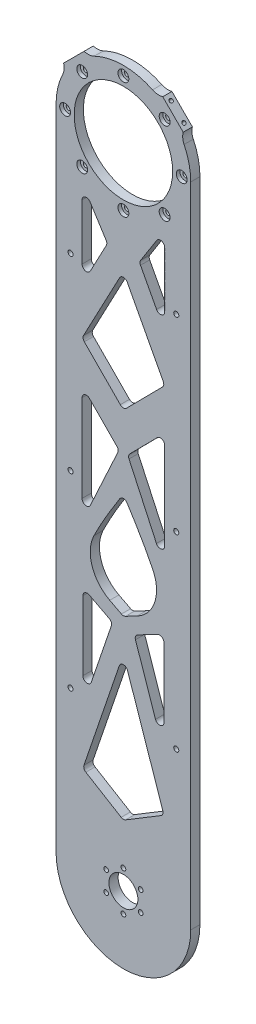
SolidWorks part; units mm, degrees
material "6061-T6 (SS)"
ref_plane "Front Plane" through (0, 0, 0) normal (0, 0, 1) x (1, 0, 0)
ref_plane "Top Plane" through (0, 0, 0) normal (0, 1, 0) x (1, 0, 0)
ref_plane "Right Plane" through (0, 0, 0) normal (1, 0, 0) x (0, 0, -1)
sketch "Sketch2" plane through (0, 0, 0) normal (0, 0, 1) x (1, 0, 0)
  line L0 (0, 0) -> (0, 500) construction
  line L1 (-46.5, 0) -> (-46.5, 500)
  line L2 (46.5, 0) -> (46.5, 500)
  arc A0 (-46.5, 0) -> (46.5, 0) centre (0, 0) ccw
  arc A1 (46.5, 500) -> (-46.5, 500) centre (0, 500) ccw
  circle A2 centre (0, 500) radius 37.25 construction
  circle A3 centre (0, 0) radius 10
  circle A4 centre (0, 13.75) radius 1.65
  circle A5 centre (0, 0) radius 13.75 construction
  circle A6 centre (11.9078, 6.875) radius 1.65
  circle A7 centre (11.9078, -6.875) radius 1.65
  circle A8 centre (0, -13.75) radius 1.65
  circle A9 centre (-11.9078, -6.875) radius 1.65
  circle A10 centre (-11.9078, 6.875) radius 1.65
  point P3 (0, 250)
  point P27 (0, 0)
  dimension "D2" = 74.5
  dimension "D4" = 20
  dimension "D5" = 3.3
  dimension "D6" = 27.5
  dimension "D3" = 46.5
  dimension "D1" = 500
  dimension "D7" = 6
extrude "Boss-Extrude1" add sketch "Sketch2" along normal blind 6.35
sketch "Sketch4" plane through (0, 0, 6.35) normal (0, 0, 1) x (1, 0, 0)
  line L0 (0, 500) -> (0, 999.1647) construction
  line L29 (46.5, 500) -> (-46.5, 500) construction
  line L31 (28.0053, 59.376) -> (0, 42.4117)
  line L32 (0, 141.6934) -> (28.0053, 59.376)
  line L33 (-28.0053, 59.376) -> (0, 141.6934)
  line L34 (0, 42.4117) -> (-28.0053, 59.376)
  line L35 (-7.5, 156.9059) -> (-28.0053, 96.6336)
  line L36 (-28.0053, 167.5829) -> (-7.5, 156.9059)
  line L37 (-28.0053, 96.6336) -> (-28.0053, 167.5829)
  line L38 (28.0053, 167.5829) -> (7.5, 156.9059)
  line L39 (28.0053, 96.6336) -> (28.0053, 167.5829)
  line L40 (7.5, 156.9059) -> (28.0053, 96.6336)
  line L41 (0, 164.2751) -> (28.5505, 179.1412)
  line L42 (0, 164.2751) -> (-28.5505, 179.1412)
  line L43 (28.5505, 259.5868) -> (3, 314.9383)
  line L44 (28.5505, 340.7931) -> (28.5505, 259.5868)
  line L45 (3, 314.9383) -> (28.5505, 340.7931)
  line L46 (-3, 314.9383) -> (-28.5505, 340.7931)
  line L47 (-28.5505, 259.5868) -> (-3, 314.9383)
  line L48 (-28.5505, 340.7931) -> (-28.5505, 259.5868)
  line L49 (0, 423.1428) -> (-28.5505, 369.2462)
  line L50 (-28.5505, 369.2462) -> (0, 340.3557)
  line L51 (0, 340.3557) -> (28.5505, 369.2462)
  line L52 (0, 423.1428) -> (28.5505, 369.2462)
  line L53 (-28.5505, 462.0952) -> (-28.5505, 401.2902)
  line L54 (-11, 434.4215) -> (-28.5505, 462.0952)
  line L55 (-28.5505, 401.2902) -> (-11, 434.4215)
  line L56 (28.5505, 401.2902) -> (11, 434.4215)
  line L57 (28.5505, 462.0952) -> (28.5505, 401.2902)
  line L58 (11, 434.4215) -> (28.5505, 462.0952)
  arc A0 (46.5, 500) -> (-46.5, 500) centre (0, 500) ccw construction
  arc A1 (46.5, 500) -> (-46.5, 500) centre (0, 500) ccw construction
  spline S2 degree 3 poles (28.5505, 179.1412) (45.3203, 216.9857) (19.4301, 259.7903) (0, 290.0258) knots 0 0 0 0 1 1 1 1
  spline S3 degree 3 poles (-28.5505, 179.1412) (-45.3203, 216.9857) (-19.4301, 259.7903) (0, 290.0258) knots 0 0 0 0 1 1 1 1
extrude "Cut-Extrude1" cut sketch "Sketch4" against normal blind 10
fillet "Fillet3" radius 3 30 edges at (-11, 434.4215, 3.175) (-28.5505, 401.2902, 3.175) (28.5505, 401.2902, 3.175) (11, 434.4215, 3.175) (28.5505, 462.0952, 3.175) (-28.5505, 462.0952, 3.175) (0, 423.1428, 3.175) (-28.5505, 369.2462, 3.175) (28.5505, 369.2462, 3.175) (0, 340.3557, 3.175) (28.5505, 340.7931, 3.175) (-28.5505, 340.7931, 3.175) (-3, 314.9383, 3.175) (3, 314.9383, 3.175) (28.5505, 259.5868, 3.175) (-28.5505, 259.5868, 3.175) (28.5505, 179.1412, 3.175) (0, 290.0258, 3.175) (-28.5505, 179.1412, 3.175) (0, 164.2751, 3.175) (-28.0053, 96.6336, 3.175) (28.0053, 96.6336, 3.175) (7.5, 156.9059, 3.175) (-28.0053, 167.5829, 3.175) (28.0053, 167.5829, 3.175) (0, 141.6934, 3.175) (28.0053, 59.376, 3.175) (-28.0053, 59.376, 3.175) (0, 42.4117, 3.175) (-7.5, 156.9059, 3.175)
sketch "Sketch5" plane through (0, 0, 6.35) normal (0, 0, 1) x (1, 0, 0)
  line L0 (0, -46.5) -> (108.8395, -46.5) construction
  line L1 (46.5, 100) -> (-46.5, 100) construction
  line L2 (46.5, 0) -> (46.5, 500) construction
  line L3 (-46.5, 500) -> (-46.5, 0) construction
  line L4 (-46.5, 106.35) -> (46.5, 106.35) construction
  line L5 (36.5, 106.35) -> (36.5, 100) construction
  line L6 (0, 106.35) -> (0, 100) construction
  line L7 (-46.5, 256.35) -> (46.5, 256.35) construction
  line L8 (-46.5, 181.35) -> (46.5, 181.35) construction
  line L9 (-46.5, 337.7) -> (46.5, 337.7) construction
  arc A1 (-46.5, 0) -> (46.5, 0) centre (0, 0) ccw construction
  circle A2 centre (36.5, 103.175) radius 1.75
  circle A3 centre (-36.5, 103.175) radius 1.75
  circle A4 centre (36.5, 259.525) radius 1.75
  circle A5 centre (-36.5, 259.525) radius 1.75
  circle A6 centre (36.5, 415.875) radius 1.75
  circle A7 centre (-36.5, 415.875) radius 1.75
  point P18 (36.5, 103.175)
  dimension "D2" = 3.5
  dimension "D1" = 146.5
  dimension "D3" = 10
  dimension "D4" = 6.35
  dimension "D5" = 150
  dimension "D6" = 81.35
  dimension "D7" = 81.35
extrude "Cut-Extrude2" cut sketch "Sketch5" against normal through all
sketch "Sketch6" plane through (0, 0, 6.35) normal (0, 0, 1) x (1, 0, 0)
  circle A0 centre (0, 500) radius 26.5
  arc A1 (46.5, 500) -> (-46.5, 500) centre (0, 500) ccw construction
  arc A2 (46.5, 500) -> (-46.5, 500) centre (0, 500) ccw construction
  dimension "D1" = 20
extrude "Cut-Extrude3" cut sketch "Sketch6" against normal blind 10
sketch "Sketch7" plane through (0, 0, 6.35) normal (0, 0, 1) x (1, 0, 0)
  line L1 (40.0163, 523.6842) -> (44.1104, 529.9682) construction
  line L2 (23.6842, 540.0163) -> (29.9682, 544.1104) construction
  line L3 (44.1104, 529.9682) -> (29.9682, 544.1104)
  line L4 (0, 500) -> (37.0393, 537.0393) construction
  line L5 (0, 500) -> (0, 546.5) construction
  arc A0 (46.5, 500) -> (-46.5, 500) centre (0, 500) ccw construction
  arc A1 (29.9682, 544.1104) -> (16.4747, 543.4837) centre (22.4977, 559.381) cw
  arc A2 (44.1104, 529.9682) -> (43.4837, 516.4747) centre (59.381, 522.4977) ccw
  arc A3 (16.4747, 543.4837) -> (43.4837, 516.4747) centre (0, 500) cw
  dimension "D3" = 17
  dimension "D5" = 17
  dimension "D1" = 20
  dimension "D2" = 7.5
  dimension "D4" = 8
  dimension "D6" = 8
  dimension "D7" = 45
extrude "Boss-Extrude2" add sketch "Sketch7" against normal up to surface (6.35 mm away) up to face at (26.5, 500, 0)
sketch "Sketch8" plane through (287.0393, 287.0393, 0) normal (0.7071, 0.7071, 0) x (0, 0, -1)
  line L0 (0, 363.5534) -> (-6.35, 363.5534) construction
  line L1 (0, 343.5534) -> (-6.35, 343.5534) construction
  line L2 (-6.35, 343.5534) -> (-6.35, 363.5534) construction
  point P0 (-3.175, 359.5534)
  point P1 (-3.175, 347.5534)
  dimension "D1" = 4
  dimension "D2" = 4
  dimension "D3" = 3.175
hole_wizard "Tap Drill for M3x0.5 Tap1" positions "Sketch8" profile "Sketch9" hole size "M3x0.5" standard "ANSI Metric"
sketch "Sketch9" plane through (32.7967, 541.282, 3.175) normal (0, 0, 1) x (-0.7071, 0.7071, 0)
  line L0 (0, 0) -> (0, 5.7511)
  line L1 (0, 5.7511) -> (1.25, 5)
  line L2 (1.25, 5) -> (1.25, 0)
  line L5 (1.25, 0) -> (0, 0)
  line L10 (0, 5.7511) -> (-1.25, 5) construction
  line L11 (0, -6.35) -> (0, 107.95) construction
  dimension "Hole Dia." = 2.5
  dimension "Hole Depth" = 5
  dimension "Drill Angle" = 118
pattern_circular "CirPattern2" count 2 every 90 about axis through (0, 500, -3.65) along (0, 0, 1) of "Boss-Extrude2", "Tap Drill for M3x0.5 Tap1"
sketch "Sketch10" plane through (0, 0, 6.35) normal (0, 0, 1) x (1, 0, 0)
  line L0 (-43.4837, 516.4747) -> (-63.4837, 516.4747)
  line L1 (43.4837, 516.4747) -> (63.4837, 516.4747)
  arc A0 (43.4837, 516.4747) -> (-43.4837, 516.4747) centre (0, 500) ccw
  arc A1 (46.5, 500) -> (43.4837, 516.4747) centre (0, 500) ccw construction
  arc A2 (-63.4837, 516.4747) -> (63.4837, 516.4747) centre (0, 500) cw
  dimension "D1" = 19.0866
  dimension "D2" = 20
extrude "Cut-Extrude4" cut sketch "Sketch10" against normal through all
sketch "Sketch11" plane through (0, 0, 6.35) normal (0, 0, 1) x (1, 0, 0)
  circle A0 centre (0, 500) radius 34
  circle A1 centre (0, 500) radius 26.5 construction
  dimension "D1" = 68
extrude "Cut-Extrude5" cut sketch "Sketch11" against normal through all
sketch "Sketch12" plane through (0, 0, 6.35) normal (0, 0, 1) x (1, 0, 0)
  line L0 (0, 534) -> (0, 546.5) construction
  circle A0 centre (0, 500) radius 40.25 construction
  circle A1 centre (0, 500) radius 34 construction
  circle A3 centre (0, 540.25) radius 1.75
  circle A4 centre (28.461, 528.461) radius 1.75
  circle A5 centre (40.25, 500) radius 1.75
  circle A6 centre (28.461, 471.539) radius 1.75
  circle A7 centre (0, 459.75) radius 1.75
  circle A8 centre (-28.461, 471.539) radius 1.75
  circle A9 centre (-40.25, 500) radius 1.75
  circle A10 centre (-28.461, 528.461) radius 1.75
  arc A11 (46.5, 500) -> (-46.5, 500) centre (0, 500) ccw construction
  point P4 (0, 540.25)
  point P36 (0, 500)
  dimension "D1" = 3.5
  dimension "D2" = 8
extrude "Cut-Extrude6" cut sketch "Sketch12" against normal through all both and the other way through all
sketch "Sketch13" plane through (0, 0, 0) normal (0, 0, -1) x (-1, 0, 0)
  line L0 (28.984, 180.1429) -> (28.984, 234.0954) construction
  line L1 (-28.984, 180.1429) -> (-28.984, 234.0954) construction
  line L2 (46.5, 234.0954) -> (-46.5, 234.0954)
  line L3 (46.5, 500) -> (46.5, 0) construction
  line L4 (-46.5, 0) -> (-46.5, 500) construction
  line L5 (46.5, 180.1429) -> (-46.5, 180.1429)
  line L6 (-46.5, 234.0954) -> (-46.5, 180.1429)
  line L7 (46.5, 234.0954) -> (46.5, 180.1429)
  spline S0 degree 3 poles (2.5314, 286.068) (21.3968, 256.4039) (44.1773, 216.1126) (28.984, 180.1429) knots 0.042883 0.042883 0.042883 0.042883 0.991187 0.991187 0.991187 0.991187 construction
  spline S1 degree 3 poles (-28.984, 180.1429) (-44.1773, 216.1126) (-21.3968, 256.4039) (-2.5314, 286.068) knots 0.008813 0.008813 0.008813 0.008813 0.957117 0.957117 0.957117 0.957117 construction
extrude "Cut-Extrude7" cut sketch "Sketch13" against normal through all
move or copy body "Body-Move/Copy1" bodies to move or copy 111 copy no translate (0, -52.7177, 0) parameters "D1"=0, "D2"=52.7177, "D3"=0
sketch "Sketch14" plane through (0, 180.1429, 0) normal (0, 1, 0) x (1, 0, 0)
  line L0 (-28.984, 0) -> (-46.5, 0) construction
  line L1 (-46.5, 0) -> (-46.5, -6.35) construction
  line L2 (-46.5, -6.35) -> (-28.984, -6.35) construction
  line L3 (-28.984, -6.35) -> (-28.984, 0) construction
  line L4 (28.984, -6.35) -> (46.5, -6.35) construction
  line L5 (46.5, -6.35) -> (46.5, 0) construction
  line L6 (46.5, 0) -> (28.984, 0) construction
  line L7 (28.984, 0) -> (28.984, -6.35) construction
  line L8 (-28.984, 0) -> (-46.5, 0)
  line L9 (-46.5, 0) -> (-46.5, -6.35)
  line L10 (-46.5, -6.35) -> (-28.984, -6.35)
  line L11 (-28.984, -6.35) -> (-28.984, 0)
  line L12 (28.984, -6.35) -> (46.5, -6.35)
  line L13 (46.5, -6.35) -> (46.5, 0)
  line L14 (46.5, 0) -> (28.984, 0)
  line L15 (28.984, 0) -> (28.984, -6.35)
extrude "Boss-Extrude3" add sketch "Sketch14" along normal up to surface (1.2348 mm away) up to face at (37.742, 181.3777, 3.175)
sketch "Sketch15" plane through (0, 0, 0) normal (0, 0, -1) x (-1, 0, 0)
  line L0 (-1.3855, 164.9966) -> (-27.606, 178.6494) construction
  line L1 (28.984, 181.3777) -> (28.984, 180.1429)
  line L2 (-28.984, 181.3777) -> (-28.984, 180.1429) construction
  line L3 (-9.4381, 169.1895) -> (-27.606, 178.6494)
  line L4 (-28.984, 181.3777) -> (-28.984, 180.1429)
  line L5 (0, 493.7823) -> (0, -46.5) construction
  line L6 (9.4381, 169.1895) -> (27.606, 178.6494)
  arc A0 (-20.3344, 202.3794) -> (-9.4381, 169.1895) centre (2.1078, 191.3636) ccw
  arc A1 (-28.984, 180.1429) -> (-27.606, 178.6494) centre (-26.2204, 181.3103) ccw construction
  arc A2 (-28.984, 180.1429) -> (-27.606, 178.6494) centre (-26.2204, 181.3103) ccw
  arc A3 (46.5, 447.2823) -> (-46.5, 447.2823) centre (0, 447.2823) ccw construction
  arc A4 (-46.5, 0) -> (46.5, 0) centre (0, 0) ccw construction
  arc A5 (28.984, 180.1429) -> (27.606, 178.6494) centre (26.2204, 181.3103) cw
  arc A6 (20.3344, 202.3794) -> (9.4381, 169.1895) centre (-2.1078, 191.3636) cw
  spline S0 degree 3 poles (1953.7087, 263.1445) (-2215.7642, -533.3919) (2154.4506, 1213.369) (-1849.5555, -532.5784) knots -2.670349 -2.670349 -2.670349 -2.670349 4.338748 4.338748 4.338748 4.338748 only from (-28.984, 181.3777) to (-2.5314, 233.3503) construction
  spline S1 degree 3 poles (28.984, 181.3777) (26.6659, 188.5284) (23.6788, 195.566) (20.3344, 202.3794) knots 0.47109 0.47109 0.47109 0.47109 0.656208 0.656208 0.656208 0.656208
  spline S2 degree 3 poles (-28.984, 181.3777) (-26.6659, 188.5284) (-23.6788, 195.566) (-20.3344, 202.3794) knots 0.47109 0.47109 0.47109 0.47109 0.656208 0.656208 0.656208 0.656208
  dimension "D1" = 25
  dimension "D2" = 540.2823
extrude "Boss-Extrude4" add sketch "Sketch15" against normal up to surface (6.35 mm away) up to face at (2.6453, 187.7844, 6.35)
sketch "Sketch16" plane through (0, 0, 0) normal (0, 0, -1) x (-1, 0, 0)
  line L0 (36.5, 103.175) -> (36.5, 363.1573) construction
  line L1 (-36.5, 103.175) -> (-36.5, 363.1573) construction
  circle A0 centre (-36.5, 363.1573) radius 1.75 construction
  circle A1 centre (36.5, 363.1573) radius 1.75 construction
  circle A2 centre (-36.5, 103.175) radius 1.75 construction
  circle A3 centre (36.5, 103.175) radius 1.75 construction
  circle A4 centre (-36.5, 363.1573) radius 1.75 construction
  circle A5 centre (36.5, 363.1573) radius 1.75 construction
  circle A6 centre (-36.5, 103.175) radius 1.75 construction
  circle A7 centre (36.5, 103.175) radius 1.75 construction
  circle A8 centre (36.5, 233.1662) radius 1.75
  circle A9 centre (-36.5, 233.1662) radius 1.75
  point P16 (36.5, 233.1662)
  point P18 (36.5, 233.1662)
extrude "Cut-Extrude8" cut sketch "Sketch16" against normal through all
sketch "Sketch17" plane through (0, 0, 0) normal (0, 0, -1) x (-1, 0, 0)
  circle A0 centre (36.5, 206.8073) radius 1.75 construction
  circle A1 centre (-36.5, 206.8073) radius 1.75 construction
  circle A2 centre (36.5, 206.8073) radius 1.75
  circle A3 centre (-36.5, 206.8073) radius 1.75
extrude "Boss-Extrude5" add sketch "Sketch17" against normal up to surface (6.35 mm away) up to face at (-34.75, 233.1662, 6.35)
sketch "Sketch18" plane through (0, 0, 0) normal (0, 0, -1) x (-1, 0, 0)
  line L0 (0, 447.2823) -> (0, 493.7823) construction
  line L1 (0, 447.2823) -> (32.8805, 480.1628) construction
  line L2 (-10, 492.6943) -> (-10, 495.6943) construction
  line L3 (25.0401, 486.4645) -> (27.1614, 488.5858)
  line L4 (27.1614, 488.5858) -> (41.3035, 474.4437)
  line L5 (41.3035, 474.4437) -> (39.1822, 472.3224)
  line L6 (25.0401, 486.4645) -> (39.1822, 472.3224)
  line L7 (-10, 495.6943) -> (10, 495.6943) construction
  line L8 (10, 495.6943) -> (10, 492.6943) construction
  line L9 (-10, 492.6943) -> (10, 492.6943) construction
  line L10 (-39.1822, 472.3224) -> (-41.3035, 474.4437)
  line L11 (-41.3035, 474.4437) -> (-27.1614, 488.5858)
  line L12 (-27.1614, 488.5858) -> (-25.0401, 486.4645)
  line L13 (-39.1822, 472.3224) -> (-25.0401, 486.4645)
  arc A0 (46.5, 447.2823) -> (-46.5, 447.2823) centre (0, 447.2823) ccw construction
  point P11 (32.1111, 479.3934)
  point P13 (0, 492.6943)
  dimension "D1" = 45
  dimension "D2" = 20
  dimension "D3" = 3
  dimension "D4" = 3
extrude "Boss-Extrude6" add sketch "Sketch18" against normal up to surface (6.35 mm away) up to face at (-34.75, 233.1662, 6.35)
sketch "Sketch20" plane through (-257.8736, 257.8736, 0) normal (-0.7071, 0.7071, 0) x (0, 0, 1)
  line L0 (6.35, 316.2764) -> (0, 316.2764) construction
  line L1 (6.35, 306.2764) -> (6.35, 326.2764) construction
  line L2 (0, 306.2764) -> (0, 326.2764) construction
  point P0 (3.175, 322.5264)
  point P9 (3.175, 316.2764)
  point P10 (3.175, 310.0264)
  dimension "D1" = 12.5
hole_wizard "M3x0.5 Tapped Hole1" positions "Sketch20" profile "Sketch21" tap size "M3x0.5" standard "ANSI Metric"
sketch "Sketch21" plane through (-29.813, 485.9342, 3.175) normal (0, 0, 1) x (-0.7071, -0.7071, 0)
  line L0 (0, 0) -> (0, 8.2511)
  line L1 (0, 8.2511) -> (1.25, 7.5)
  line L2 (1.25, 7.5) -> (1.25, 0)
  line L5 (1.25, 0) -> (0, 0)
  line L10 (0, 8.2511) -> (-1.25, 7.5) construction
  line L11 (0, -6.35) -> (0, 107.95) construction
  dimension "Tap Drill Dia." = 2.5
  dimension "Tap Drill Depth" = 7.5
  dimension "Drill Angle" = 118
cosmetic thread "Hole Thread1" parameters "D1"=6, "D2"=3
cosmetic thread "Hole Thread2" parameters "D1"=6, "D2"=3
pattern_circular "CirPattern3" count 2 over 90 about axis through (0, 447.2823, 0) along (0, 0, 1) of "M3x0.5 Tapped Hole1" reverse direction yes
cosmetic thread "Hole Thread5" parameters "D1"=6, "D2"=3
cosmetic thread "Hole Thread6" parameters "D1"=6, "D2"=3
cosmetic thread "Hole Thread7" parameters "D1"=6, "D2"=3
cosmetic thread "Hole Thread8" parameters "D1"=6, "D2"=3
fillet "Fillet4" radius 10 4 edges at (-39.1822, 472.3224, 3.175) (-25.0401, 486.4645, 3.175) (39.1822, 472.3224, 3.175) (25.0401, 486.4645, 3.175)
sketch "Sketch22" plane through (0, 0, 6.35) normal (0, 0, 1) x (1, 0, 0)
  circle A0 centre (0, 487.5323) radius 1.75 construction
  circle A1 centre (0, 487.5323) radius 1.75 construction
  circle A2 centre (0, 487.5323) radius 3.75
  dimension "D1" = 7.5
extrude "shallow_counterbore" cut sketch "Sketch22" against normal blind 2.5
pattern_circular "shallow_counterbore_2" count 8 over 360 about axis through (0, 447.2823, 0) along (0, 0, 1) of "shallow_counterbore"
equation "\"L1L\"=500"
equation "\"L1Thick\"=6.35"
equation "\"D1@Sketch2\"=\"L1L\""
equation "\"Harm-Drive-Outer\"=74.5"
equation "\"D2@Sketch2\"=\"Harm-Drive-Outer\""
equation "\"D1@Boss-Extrude1\"=\"L1Thick\""
